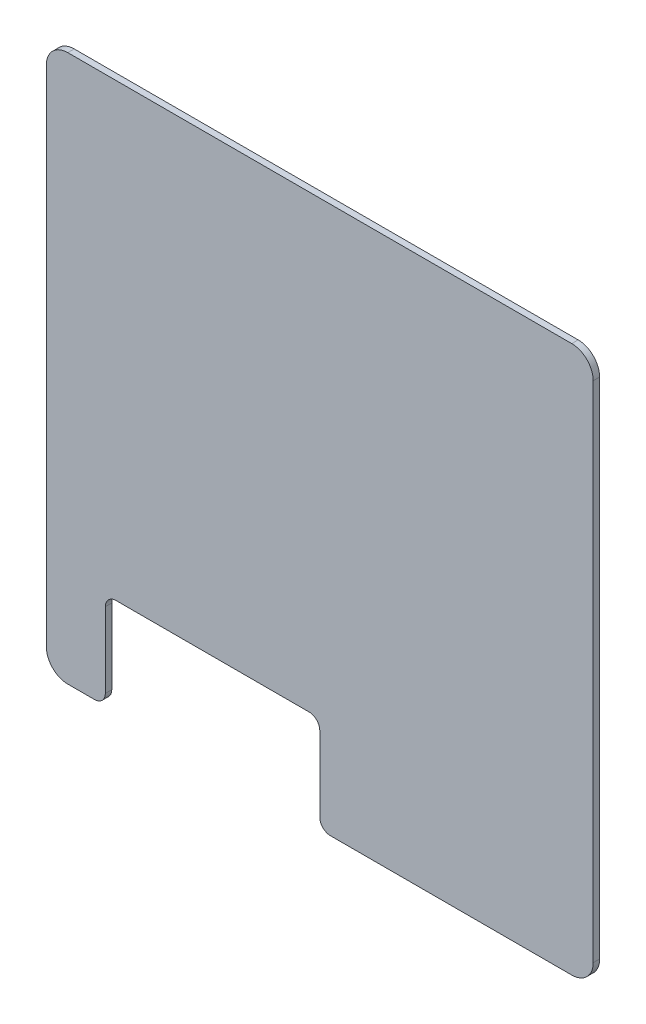
SolidWorks part; units mm, degrees
material "Pine"
ref_plane "Front Plane" through (0, 0, 0) normal (0, 0, 1) x (1, 0, 0)
ref_plane "Top Plane" through (0, 0, 0) normal (0, 1, 0) x (1, 0, 0)
ref_plane "Right Plane" through (0, 0, 0) normal (1, 0, 0) x (0, 0, -1)
sketch "Sketch1" plane through (0, 0, 0) normal (0, 0, 1) x (1, 0, 0)
  line L1 (-250, 250) -> (250, 250) construction
  line L2 (-250, 250) -> (-250, -250) construction
  line L3 (-250, -250) -> (250, -250) construction
  line L4 (250, 250) -> (250, -250) construction
  line L5 (-250, 250) -> (250, -250) construction
  line L6 (-250, -250) -> (250, 250) construction
  line L7 (255, 255) -> (-255, 255)
  line L8 (255, 255) -> (255, -255)
  line L9 (255, -255) -> (-255, -255)
  line L10 (-255, 255) -> (-255, -255)
  line L11 (255, 255) -> (-255, -255) construction
  line L12 (255, -255) -> (-255, 255) construction
  point P0 (0, 0)
  point P5 (0, 0)
  dimension "D1" = 500
  dimension "D2" = 500
  dimension "D3" = 510
extrude "Boss-Extrude1" add sketch "Sketch1" along normal blind 6
sketch "Sketch2" plane through (0, 0, 6) normal (0, 0, 1) x (1, 0, 0)
  line L0 (-255, -255) -> (255, -255) construction
  line L1 (-200, -255) -> (0, -255)
  line L2 (-200, -255) -> (-200, -165)
  line L3 (-200, -165) -> (0, -165)
  line L4 (0, -255) -> (0, -165)
  dimension "D2" = 200
  dimension "D3" = 90
extrude "Cut-Extrude1" cut sketch "Sketch2" against normal blind 6
fillet "Fillet2" radius 20 4 edges at (255, 255, 3) (255, -255, 3) (-255, 255, 3) (-255, -255, 3)
fillet "Fillet3" radius 10 4 edges at (0, -255, 3) (0, -165, 3) (-200, -255, 3) (-200, -165, 3)
sketch "Sketch3" plane through (0, 0, 6) normal (0, 0, 1) x (1, 0, 0)
  line L1 (-250, 250) -> (250, 250)
  line L2 (-250, 250) -> (-250, -250)
  line L3 (-250, -250) -> (250, -250)
  line L4 (250, 250) -> (250, -250)
  line L5 (-250, 250) -> (250, -250) construction
  line L6 (-250, -250) -> (250, 250) construction
  dimension "D1" = 500
